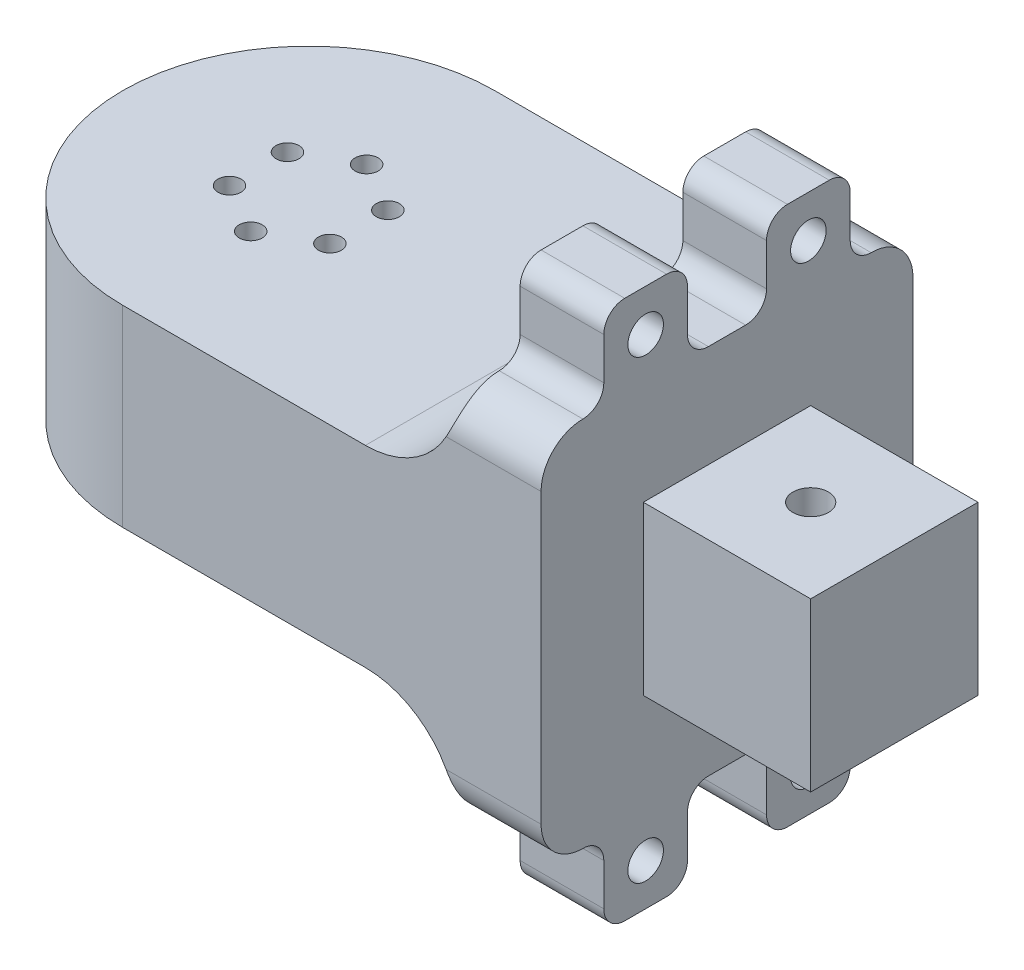
SolidWorks part; units mm, degrees
ref_plane "Front Plane" through (0, 0, 0) normal (0, 0, 1) x (1, 0, 0)
ref_plane "Top Plane" through (0, 0, 0) normal (0, 1, 0) x (1, 0, 0)
ref_plane "Right Plane" through (0, 0, 0) normal (1, 0, 0) x (0, 0, -1)
sketch "Sketch1" plane through (0, 0, 0) normal (0, 1, 0) x (1, 0, 0)
  line L0 (0, 44.45) -> (80, 44.45)
  line L1 (80, 44.45) -> (80, -44.45)
  line L2 (80, -44.45) -> (0, -44.45)
  arc A0 (0, 44.45) -> (0, -44.45) centre (0, 0) ccw
  dimension "D1" = 44.45
  dimension "D2" = 80
extrude "Boss-Extrude1" add sketch "Sketch1" along normal blind 46
sketch "Sketch2" plane through (0, 0, 0) normal (0, -1, 0) x (-1, 0, 0)
  line L1 (0, -13.8564) -> (12, -6.9282)
  line L2 (12, -6.9282) -> (12, 6.9282)
  line L3 (12, 6.9282) -> (0, 13.8564)
  line L4 (0, 13.8564) -> (-12, 6.9282)
  line L5 (-12, 6.9282) -> (-12, -6.9282)
  line L6 (-12, -6.9282) -> (0, -13.8564)
  circle A0 centre (0, 0) radius 12 construction
  circle A1 centre (0, -13.8564) radius 2.75
  circle A2 centre (12, -6.9282) radius 2.75
  circle A3 centre (12, 6.9282) radius 2.75
  circle A4 centre (0, 13.8564) radius 2.75
  circle A5 centre (-12, 6.9282) radius 2.75
  circle A6 centre (-12, -6.9282) radius 2.75
extrude "Cut-Extrude2" cut sketch "Sketch2" against normal blind 76 contours L6 A1 L1 | L5 A6 L6 | L4 A5 L5 | L3 A4 L4 | L2 A3 L3 | L1 A2 L2 | L2 A2 L1 | L1 A1 L6 | L6 A6 L5 | L5 A5 L4 | L4 A4 L3 | L3 A3 L2 region at (0, 0, 12.3403) region at (0, 0, 14.6145) region at (-10.687, 0, 6.1701) region at (-12.6565, 0, 7.3072) region at (12.6565, 0, 7.3072) region at (10.687, 0, 6.1701) region at (-10.687, 0, -6.1701) region at (-12.6565, 0, -7.3072) region at (12.6565, 0, -7.3072) region at (10.687, 0, -6.1701) region at (0, 0, -12.3403) region at (0, 0, -14.6145)
sketch "Sketch3" plane through (80, 0, 0) normal (1, 0, 0) x (0, 0, -1)
  line L2 (-44.45, 67.45) -> (-44.45, -21.45)
  line L4 (-44.45, 67.45) -> (44.45, 67.45)
  line L5 (44.45, 67.45) -> (44.45, -21.45)
  line L6 (-44.45, -21.45) -> (44.45, -21.45)
  dimension "D1" = 88.9
  dimension "D2" = 88.9
extrude "Boss-Extrude2" add sketch "Sketch3" along normal blind 20
fillet "Fillet1" radius 22 2 edges at (80, 46, 0) (80, 0, 0)
sketch "Sketch5" plane through (100, 0, 0) normal (1, 0, 0) x (0, 0, -1)
  line L0 (0, 23) -> (0, 43)
  line L1 (0, 43) -> (-20, 43)
  line L2 (-20, 43) -> (-20, 3)
  line L3 (-20, 3) -> (20, 3)
  line L4 (20, 3) -> (20, 43)
  line L5 (20, 43) -> (0, 43)
  dimension "D1" = 20
extrude "Boss-Extrude3" add sketch "Sketch5" along normal blind 40 contours L4 L5 L1 L2 L3 region at (100, 42.4343, -10)
sketch "Sketch6" plane through (0, 43, 0) normal (0, 1, 0) x (1, 0, 0)
  line L0 (140, 20) -> (140, -20) construction
  circle A0 centre (120, 0) radius 4.25
  dimension "D1" = 20
extrude "Cut-Extrude3" cut sketch "Sketch6" against normal blind 67
sketch "Sketch7" plane through (0, 67.45, 0) normal (0, 1, 0) x (1, 0, 0)
  line L0 (80, 44.45) -> (80, -44.45) construction
  line L1 (80, 29.45) -> (100, 29.45)
  line L2 (80, 29.45) -> (80, 9.45)
  line L3 (80, 9.45) -> (100, 9.45)
  line L4 (100, 29.45) -> (100, 9.45)
  line L5 (100, 20) -> (100, -20) construction
  line L6 (100, 44.45) -> (80, 44.45) construction
  line L7 (100, 44.45) -> (100, -44.45) construction
  line L8 (80, -9.45) -> (100, -9.45)
  line L9 (80, -9.45) -> (80, -29.45)
  line L10 (80, -29.45) -> (100, -29.45)
  line L11 (100, -9.45) -> (100, -29.45)
  line L12 (100, -44.45) -> (80, -44.45) construction
  dimension "D1" = 20
  dimension "D2" = 15
  dimension "D3" = 20
  dimension "D4" = 15
extrude "Boss-Extrude4" add sketch "Sketch7" along normal blind 20
sketch "Sketch8" plane through (0, -21.45, 0) normal (0, -1, 0) x (1, 0, 0)
  line L0 (80, 44.45) -> (80, -44.45) construction
  line L1 (80, 29.45) -> (100, 29.45)
  line L2 (80, 29.45) -> (80, 9.45)
  line L3 (80, 9.45) -> (100, 9.45)
  line L4 (100, 29.45) -> (100, 9.45)
  line L5 (100, 44.45) -> (100, -44.45) construction
  line L6 (100, 44.45) -> (80, 44.45) construction
  line L7 (100, 20) -> (100, -20) construction
  line L8 (80, -29.45) -> (100, -29.45)
  line L9 (80, -29.45) -> (80, -9.45)
  line L10 (80, -9.45) -> (100, -9.45)
  line L11 (100, -29.45) -> (100, -9.45)
  line L12 (100, -44.45) -> (80, -44.45) construction
  dimension "D1" = 20
  dimension "D2" = 15
  dimension "D3" = 20
  dimension "D4" = 15
extrude "Boss-Extrude5" add sketch "Sketch8" along normal blind 20
fillet "Fillet2" radius 5 16 edges at (90, -41.45, -29.45) (90, -41.45, 29.45) (90, 87.45, -9.45) (90, 87.45, -29.45) (90, 87.45, 9.45) (90, 87.45, 29.45) (90, -41.45, -9.45) (90, -41.45, 9.45) (90, -21.45, -29.45) (90, -21.45, -9.45) (90, -21.45, 9.45) (90, -21.45, 29.45) (90, 67.45, 29.45) (90, 67.45, -29.45) (90, 67.45, -9.45) (90, 67.45, 9.45)
fillet "Fillet3" radius 10 4 edges at (90, -21.45, -44.45) (90, 67.45, -44.45) (90, 67.45, 44.45) (90, -21.45, 44.45)
sketch "Sketch10" plane through (80, 0, 0) normal (-1, 0, 0) x (0, 0, 1)
  line L0 (-24.45, 87.45) -> (-14.45, 87.45) construction
  line L1 (-9.45, 82.45) -> (-9.45, 72.45) construction
  line L2 (9.45, 82.45) -> (9.45, 72.45) construction
  line L3 (14.45, 87.45) -> (24.45, 87.45) construction
  line L4 (29.45, -36.45) -> (29.45, -26.45) construction
  line L5 (24.45, -41.45) -> (14.45, -41.45) construction
  line L6 (-14.45, -41.45) -> (-24.45, -41.45) construction
  line L7 (-29.45, -36.45) -> (-29.45, -26.45) construction
  circle A0 centre (-19.45, 77.45) radius 4.25
  circle A1 centre (19.45, 77.45) radius 4.25
  circle A2 centre (19.45, -31.45) radius 4.25
  circle A3 centre (-19.45, -31.45) radius 4.25
  point P22 (0, 0)
  point P24 (-16.5274, -32.4359)
  dimension "D1" = 10
  dimension "D2" = 10
  dimension "D3" = 10
  dimension "D4" = 10
  dimension "D5" = 10
  dimension "D6" = 10
  dimension "D7" = 10
  dimension "D8" = 10
extrude "Cut-Extrude4" cut sketch "Sketch10" against normal blind 20
